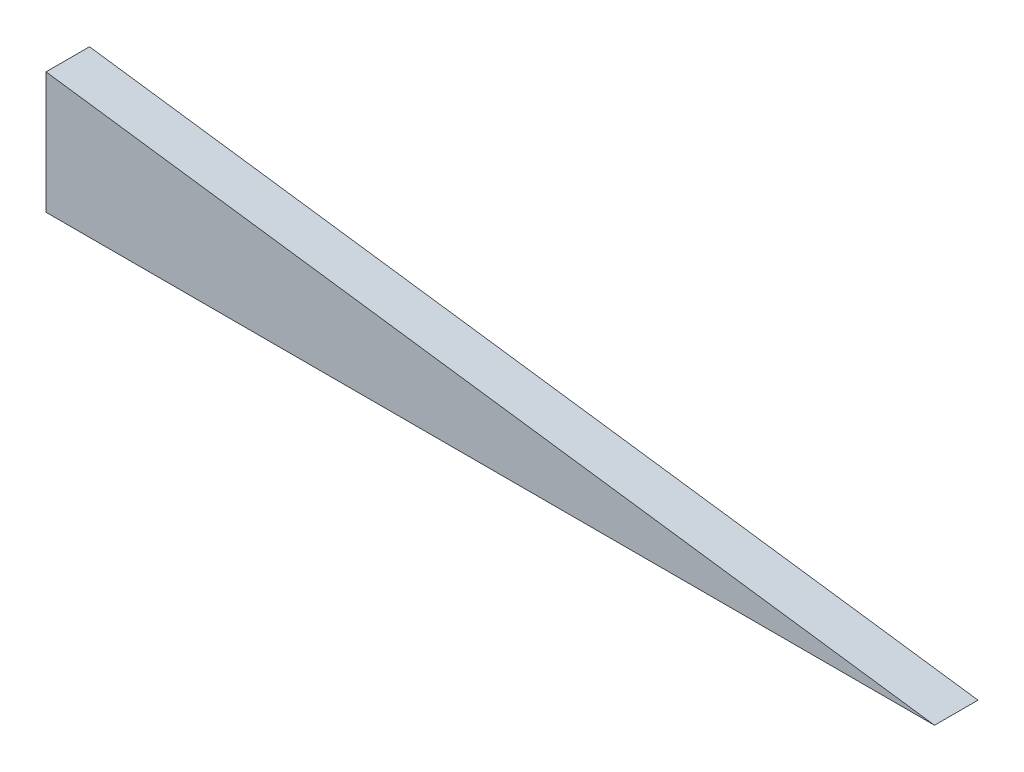
SolidWorks part; units mm, degrees
ref_plane "Front Plane" through (0, 0, 0) normal (0, 0, 1) x (1, 0, 0)
ref_plane "Top Plane" through (0, 0, 0) normal (0, 1, 0) x (1, 0, 0)
ref_plane "Right Plane" through (0, 0, 0) normal (1, 0, 0) x (0, 0, -1)
sketch "Sketch1" plane through (0, 0, 0) normal (0, 0, 1) x (1, 0, 0)
  line L0 (0, 0) -> (-108.966, 0)
  line L1 (-108.966, 14.9148) -> (0, 0)
  line L2 (-108.966, 0) -> (-108.966, 14.9148)
  dimension "D1" = 109.982
  dimension "D2" = 108.966
extrude "Boss-Extrude1" add sketch "Sketch1" along normal mid plane 5.334
equation "\"material\"=\"GMaterial@Platform.assembly\""
equation "\"D1@Boss-Extrude1\"=\"material\""
